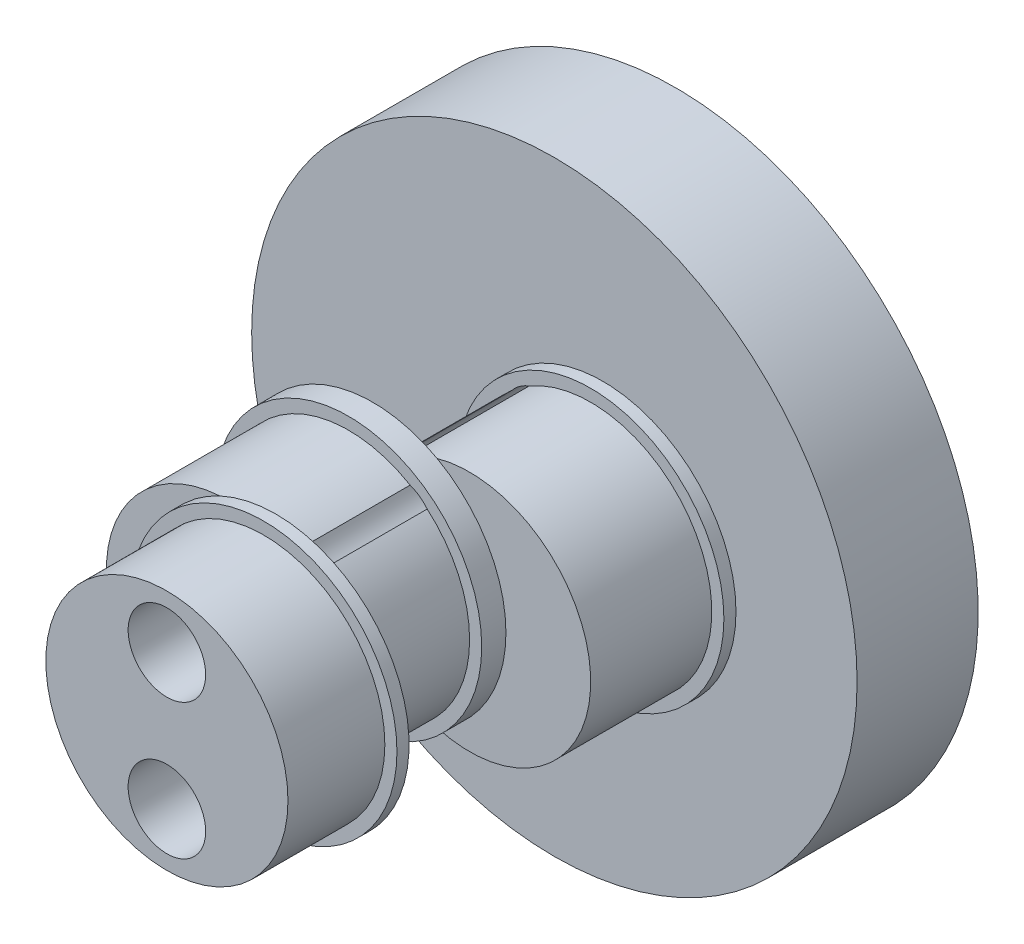
SolidWorks part; units mm, degrees
ref_plane "Front Plane" through (0, 0, 0) normal (0, 0, 1) x (1, 0, 0)
ref_plane "Top Plane" through (0, 0, 0) normal (0, 1, 0) x (1, 0, 0)
ref_plane "Right Plane" through (0, 0, 0) normal (1, 0, 0) x (0, 0, -1)
sketch "Sketch1" plane through (0, 0, -2) normal (0, 0, -1) x (-1, 0, 0)
  circle A0 centre (0, 0) radius 12.5
  dimension "D1" = 25
extrude "Boss-Extrude1" add sketch "Sketch1" against normal up to surface (5 mm away) contours A0
sketch "Sketch2" plane through (0, 0, 3) normal (0, 0, 1) x (1, 0, 0)
  line L0 (0, 0) -> (2, 0)
  circle A0 centre (2, 0) radius 5
  circle A1 centre (2, 0) radius 5.4995
  dimension "D2" = 10
extrude "Boss-Extrude2" add sketch "Sketch2" along normal blind 0.5 contours A1 A0 region at (-3.3439, 0, 3)
extrude "Boss-Extrude3" add sketch "Sketch2<3>" along normal blind 5.5 contours A0 region at (-2.8586, 0, 3)
sketch "Sketch2<3>" plane through (0, 0, 3) normal (0, 0, 1) x (1, 0, 0) same geometry as "Sketch2"
sketch "Sketch3" plane through (0, 0, 3) normal (0, 0, 1) x (1, 0, 0)
  line L0 (0, 0) -> (-2, 0)
  circle A0 centre (-2, 0) radius 5
  circle A1 centre (-2, 0) radius 5.5
  circle M1 centre (2, 0) radius 5.4995
  dimension "D2" = 10
  dimension "D3" = 11
extrude "Boss-Extrude4" add sketch "Sketch3" along normal blind 1 from surface contours A1 A0 M1 | A1 A0 M1 region at (2.0707, 3.0899, 3) region at (-7.1331, 0, 3) starting at face at (7, 0, 8.5)
extrude "Boss-Extrude5" add sketch "Sketch3<3>" along normal blind 6 from surface contours A0 M1 | A0 region at (1.8901, -2.9528, 3) region at (-4.3558, 0, 3) starting at face at (7, 0, 8.5)
sketch "Sketch3<3>" plane through (0, 0, 3) normal (0, 0, 1) x (1, 0, 0) same geometry as "Sketch3"
sketch "Sketch4" plane through (0, 0, 3) normal (0, 0, 1) x (1, 0, 0)
  circle A0 centre (0, 0) radius 5
  circle A1 centre (0, 0) radius 5.5
  dimension "D1" = 10
  dimension "D2" = 11
extrude "Boss-Extrude6" add sketch "Sketch4" along normal blind 0.5 from surface starting at face at (3, 0, 14.5)
extrude "Boss-Extrude7" add sketch "Sketch4<7>" along normal blind 4.5 from surface contours A0 starting at face at (-6.25, 0, 14.5)
sketch "Sketch4<7>" plane through (0, 0, 3) normal (0, 0, 1) x (1, 0, 0) same geometry as "Sketch4"
sketch "Sketch5" plane through (0, 0, 19) normal (0, 0, 1) x (1, 0, 0)
  line L1 (0, 2.8) -> (0, 0) construction
  line L2 (0, 0) -> (0, -2.8) construction
  circle A0 centre (0, 2.8) radius 1.6
  circle A1 centre (0, -2.8) radius 1.6
  dimension "D3" = 3.2
  dimension "D4" = 3.2
  dimension "D1" = 2.8
  dimension "D2" = 2.8
extrude "Cut-Extrude1" cut sketch "Sketch5" against normal through all
equation "\"CenterShaft\"=25"
equation "\"D1@Sketch1\"=\"CenterShaft\""
equation "\"Eccentricity\"=2"
equation "\"D1@Sketch2\"=\"Eccentricity\""
equation "\"CycCamShaft\"=10"
equation "\"D2@Sketch2\"=\"CycCamShaft\""
equation "\"D2@Sketch3\"=\"CycCamShaft\""
equation "\"D1@Sketch4\"=\"CycCamShaft\""
equation "\"RingPinShaft\"= 5"
equation "\"CenterBearingOut\"=32"
equation "\"RingPostIn\"=5"
equation "\"CamBearingOut\"=15.15"
equation "\"DiskOutputShaft\"=10"
